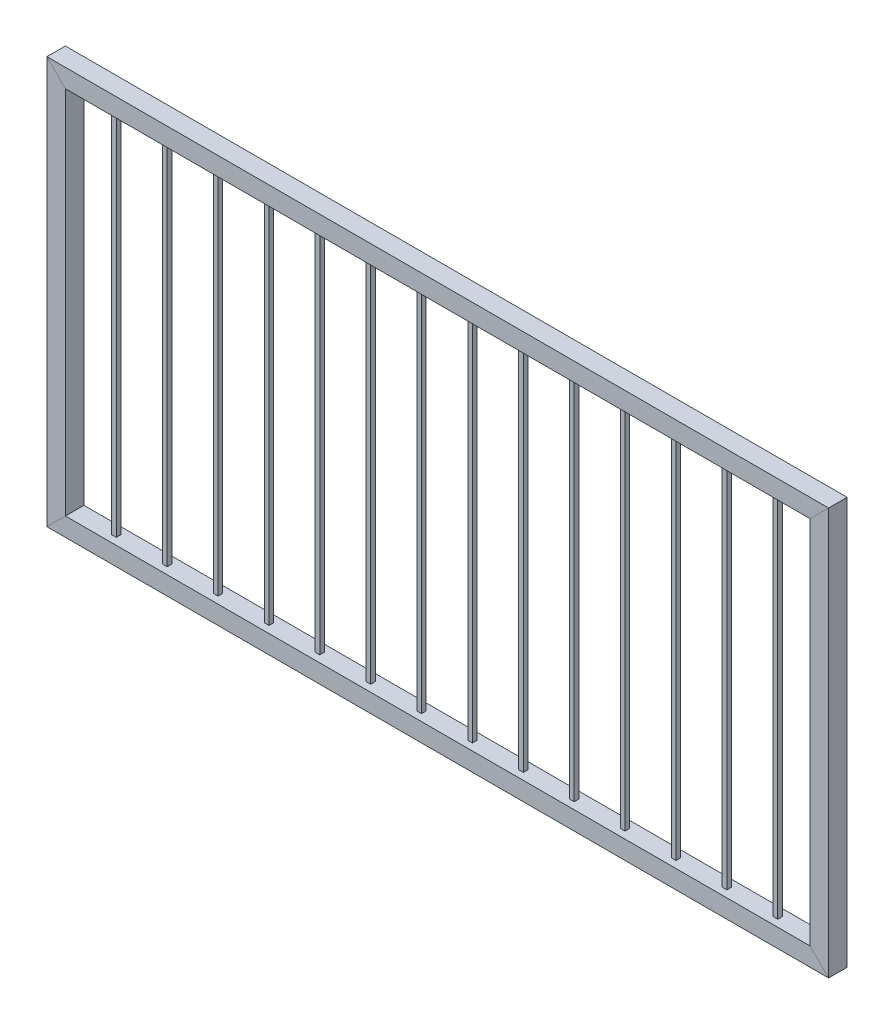
SolidWorks part; units mm, degrees
material "AISI 1020"
ref_plane "Спереди" through (0, 0, 0) normal (0, 0, 1) x (1, 0, 0)
ref_plane "Сверху" through (0, 0, 0) normal (0, 1, 0) x (1, 0, 0)
ref_plane "Справа" through (0, 0, 0) normal (1, 0, 0) x (0, 0, -1)
other "Configuration Table"
sketch3d "Трехмерный эскиз1"
  line L0 (0, 0, 0) -> (0, 840, 0)
  line L1 (0, 840, 0) -> (1650, 840, 0)
  line L2 (0, 0, 0) -> (1650, 0, 0)
  line L3 (1650, 0, 0) -> (1650, 840, 0)
  line L4 (0, 840, 0) -> (-20, 840, 0) construction
  line L5 (1650, 840, 0) -> (1670, 840, 0) construction
  line L6 (0, 840, 0) -> (0, 860, 0) construction
  line L7 (0, 0, 0) -> (0, -20, 0) construction
  dimension "D1" = 20
  dimension "D3" = 1690
  dimension "D2" = 20
  dimension "D4" = 880
sketch "Эскиз1" plane through (0, 0, 0) normal (0, 1, 0) x (1, 0, 0)
  line L1 (-20, -20) -> (20, -20)
  line L2 (-20, -20) -> (-20, 20)
  line L3 (-20, 20) -> (20, 20)
  line L4 (20, -20) -> (20, 20)
  line L5 (-20, -20) -> (20, 20) construction
  line L6 (-20, 20) -> (20, -20) construction
  point P0 (0, 0)
  dimension "D1" = 40
sweep "По траектории1" add profiles "Эскиз1" path "Трехмерный эскиз1"
ref_plane "Плоскость1" through (825, 0, 0) normal (-1, 0, 0) x (0, 0, 1)
ref_plane "Плоскость2" through (0, 0, 0) normal (0, 0, -1) x (-1, 0, 0)
ref_axis "Ось1" through (825, 818, 0) along (0, 1, 0)
sketch "Эскиз2" plane through (0, 20, 0) normal (0, 1, 0) x (1, 0, 0)
  line L0 (770, 0) -> (825, 0) construction
  line L1 (765, 5) -> (775, 5)
  line L2 (765, 5) -> (765, -5)
  line L3 (765, -5) -> (775, -5)
  line L4 (775, 5) -> (775, -5)
  line L5 (765, 5) -> (775, -5) construction
  line L6 (765, -5) -> (775, 5) construction
  point P0 (770, 0)
  dimension "D1" = 55
  dimension "D2" = 10
extrude "Бобышка-Вытянуть1" add sketch "Эскиз2" along normal up to surface (800 mm away) up to face at (825, 820, 0)
pattern_linear "Линейный массив1" count 7 spacing 110 along (-1, 0, 0) of "Бобышка-Вытянуть1"
mirror "Зеркальное отражение1" about plane through (825, 0, 0) normal (-1, 0, 0) of "Линейный массив1", "Бобышка-Вытянуть1"
